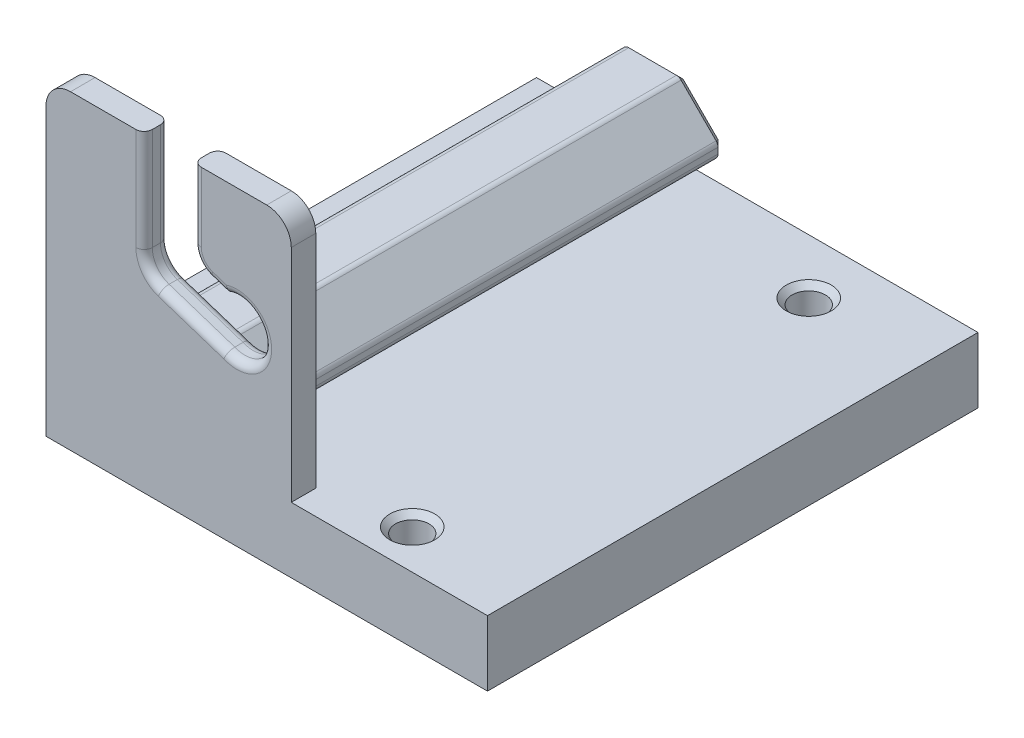
SolidWorks part; units mm, degrees
ref_plane "Front" through (0, 0, 0) normal (0, 0, 1) x (1, 0, 0)
ref_plane "Top" through (0, 0, 0) normal (0, 1, 0) x (1, 0, 0)
ref_plane "Right" through (0, 0, 0) normal (1, 0, 0) x (0, 0, -1)
sketch "Sketch1" plane through (0, 0, 0) normal (0, 0, 1) x (1, 0, 0)
  line L0 (54, 0) -> (54, 8)
  line L1 (0, 0) -> (54, 0)
  line L2 (0, 0) -> (0, 38)
  line L3 (0, 38) -> (30, 38)
  line L5 (54, 8) -> (30, 8)
  line L6 (30, 8) -> (30, 38)
  dimension "D1" = 38
  dimension "D2" = 30
  dimension "D3" = 54
  dimension "D4" = 8
extrude "Boss-Extrude1" add sketch "Sketch1" along normal blind 3
sketch "Sketch2" plane through (0, 0, 0) normal (0, 0, -1) x (-1, 0, 0)
  line L0 (0, 38) -> (0, 0) construction
  line L1 (-54, 0) -> (0, 0)
  line L2 (-54, 0) -> (-54, 8)
  line L3 (-54, 8) -> (0, 8)
  line L4 (0, 0) -> (0, 8)
  dimension "D1" = 8
extrude "Boss-Extrude2" add sketch "Sketch2" along normal blind 57
sketch "Sketch3" plane through (0, 0, 0) normal (0, -1, 0) x (1, 0, 0)
  line L0 (40, -1.8) -> (40, -50.3) construction
  line L1 (0, 3) -> (0, -57) construction
  line L2 (0, 3) -> (54, 3) construction
  circle A0 centre (40, -1.8) radius 2.05
  circle A1 centre (40, -50.3) radius 2.05
  dimension "D4" = 4.1
  dimension "D5" = 4.1
  dimension "D1" = 40
  dimension "D2" = 48.5
  dimension "D3" = 4.8
extrude "Cut-Extrude1" cut sketch "Sketch3" against normal blind 57
sketch "Sketch4" plane through (0, 0, 0) normal (0, 0, -1) x (-1, 0, 0)
  line L0 (-18, 8) -> (-18, 11)
  line L1 (0, 8) -> (-54, 8) construction
  line L2 (-18, 11) -> (-23, 11)
  line L3 (-23, 11) -> (-23, 12.85)
  line L4 (-23, 12.85) -> (-18.25, 17.6)
  line L5 (-18.25, 17.6) -> (-11.75, 17.6)
  line L6 (-11.75, 17.6) -> (-7, 12.85)
  line L7 (-7, 12.85) -> (-7, 11)
  line L8 (-7, 11) -> (-12, 11)
  line L9 (-12, 11) -> (-12, 8)
  line L10 (-12, 8) -> (-18, 8)
  line L11 (-15, 17.6) -> (-15, 8) construction
  line L12 (-15, 38) -> (-15, 8) construction
  line L13 (-30, 38) -> (0, 38) construction
  line L14 (0, 8) -> (-30, 8) construction
  dimension "D1" = 3
  dimension "D2" = 9.6
  dimension "D3" = 45
  dimension "D4" = 45
  dimension "D5" = 6.5
  dimension "D6" = 16
  dimension "D7" = 6
extrude "Boss-Extrude3" add sketch "Sketch4" along normal blind 57
fillet "Fillet1" radius 3 2 edges at (0, 38, 1.5) (30, 38, 1.5)
sketch "Sketch5" plane through (0, 0, 3) normal (0, 0, 1) x (1, 0, 0)
  line L0 (30, 26.05) -> (27.1, 26.05) construction
  line L2 (27.1, 26.05) -> (27.1, 31.1) construction
  line L3 (27.1, 31.1) -> (24.95, 31.1) construction
  line L4 (24.95, 31.1) -> (20.1, 26.25) construction
  line L5 (20.1, 26.25) -> (20.1, 19.75) construction
  line L6 (20.1, 19.75) -> (24.95, 14.9) construction
  line L7 (24.95, 14.9) -> (27.1, 14.9) construction
  line L8 (27.1, 14.9) -> (27.1, 19.95) construction
  line L9 (27.1, 19.95) -> (30, 19.95) construction
  line L10 (30, 19.95) -> (30, 26.05) construction
  line L11 (20.1, 23) -> (30, 23) construction
  line L12 (27, 38) -> (3, 38) construction
  line L16 (30, 8) -> (30, 35) construction
  line L17 (22.1, 26) -> (20.0633, 26.6694)
  line L18 (18, 29.5194) -> (18, 38)
  line L19 (18, 38) -> (12, 38)
  line L20 (12, 38) -> (12, 25.4916)
  line L21 (14.0633, 22.6416) -> (22.1, 20)
  circle A0 centre (23.35, 23) radius 3.25 construction
  arc A1 (22.1, 26) -> (22.1, 20) centre (23.35, 23) cw
  arc A5 (18, 29.5194) -> (20.0633, 26.6694) centre (21, 29.5194) ccw
  arc A6 (12, 25.4916) -> (14.0633, 22.6416) centre (15, 25.4916) ccw
  point P22 (15, 38)
  point P23 (14.1287, 22.4196)
  point P24 (0, 0)
  point P27 (22.1, 20)
  dimension "D9" = 6.5
  dimension "D10" = 6
  dimension "D13" = 3
  dimension "D1" = 45
  dimension "D2" = 45
  dimension "D3" = 6.5
  dimension "D4" = 6.1
  dimension "D5" = 2.9
  dimension "D6" = 9.9
  dimension "D7" = 16.2
  dimension "D8" = 15
  dimension "D11" = 15
  dimension "D12" = 6
  dimension "D14" = 5.7
extrude "Cut-Extrude2" cut sketch "Sketch5" against normal blind 6
fillet "Fillet3" radius 0.8 6 edges at (23, 11, -28.5) (7, 11, -28.5) (7, 12.85, -28.5) (11.75, 17.6, -28.5) (18.25, 17.6, -28.5) (23, 12.85, -28.5)
chamfer "Chamfer1" distance 0.8 angle 45 15 edges at (12, 9.5, -57) (18, 9.5, -57) (9.9, 11, -57) (7.2343, 11.2343, -57) (7, 12.1593, -57) (7.0609, 12.8248, -57) (9.375, 15.225, -57) (20.1, 11, -57) (11.7752, 17.5391, -57) (22.7657, 11.2343, -57) (15, 17.6, -57) (23, 12.1593, -57) (18.2248, 17.5391, -57) (22.9391, 12.8248, -57) (20.625, 15.225, -57)
chamfer "Chamfer2" distance 0.7 angle 45 4 edges at (42.05, 8, -50.3) (40, 0, -52.35) (42.05, 8, -1.8) (40, 0, -3.85)
fillet "Fillet4" radius 1 7 edges at (21.0816, 26.3347, 3) (18.0816, 21.3208, 3) (12.57, 23.7323, 3) (18.57, 27.7602, 3) (18, 33.7597, 3) (26.6, 23, 3) (12, 31.7458, 3)
fillet "Fillet6" radius 1 7 edges at (18, 33.7597, 0) (18.57, 27.7602, 0) (12, 31.7458, 0) (12.57, 23.7323, 0) (26.6, 23, 0) (21.0816, 26.3347, 0) (18.0816, 21.3208, 0)
